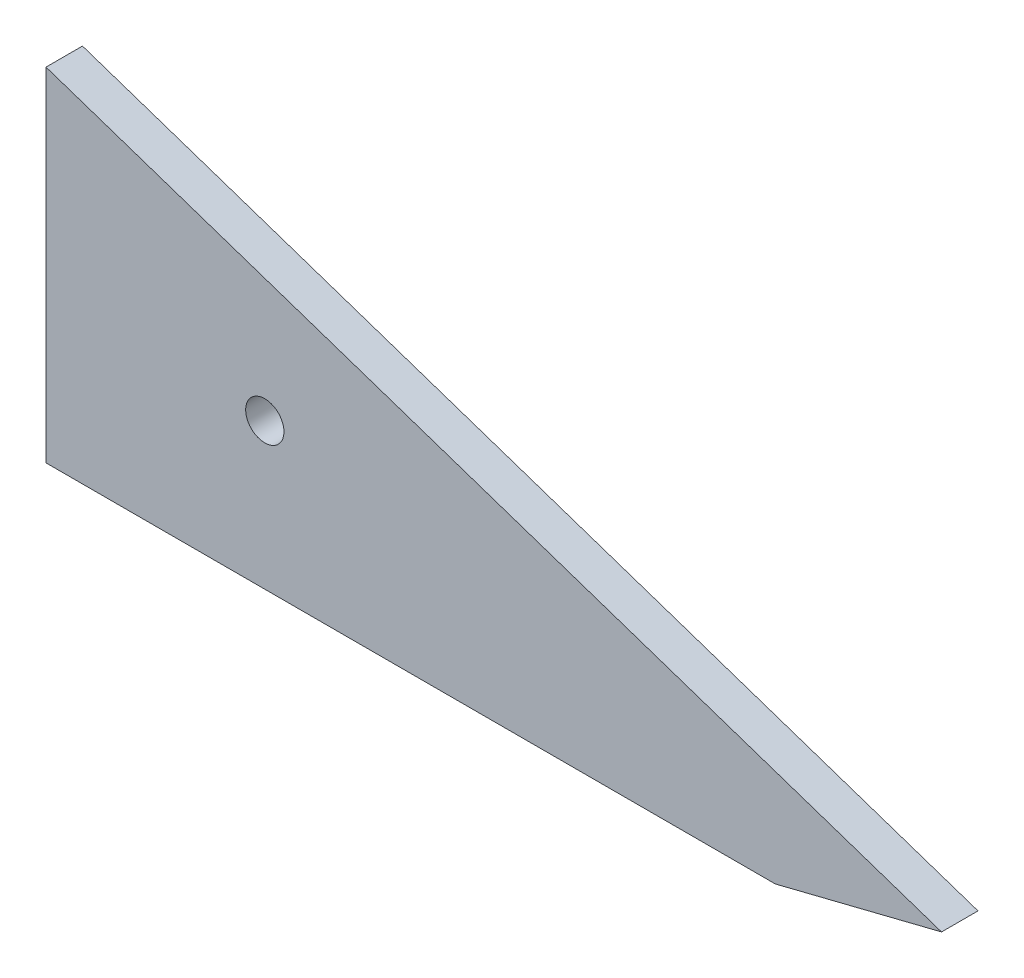
SolidWorks part; units mm, degrees
material "A516 Gr. 70 (Killed Carbon Steel)"
ref_plane "Front Plane" through (0, 0, 0) normal (0, 0, 1) x (1, 0, 0)
ref_plane "Top Plane" through (0, 0, 0) normal (0, 1, 0) x (1, 0, 0)
ref_plane "Right Plane" through (0, 0, 0) normal (1, 0, 0) x (0, 0, -1)
sketch "Sketch1" plane through (0, 0, 0) normal (0, 0, 1) x (1, 0, 0)
  line L0 (0, 0) -> (200, 0)
  line L1 (220, 5) -> (220, 20) construction
  line L2 (220, 20) -> (0, 94)
  line L3 (0, 94) -> (0, 0)
  line L4 (0, 0) -> (200, 0) construction
  line L5 (200, 0) -> (220, 5)
  line L6 (220, 0) -> (220, 5) construction
  line L7 (200, 0) -> (220, 0) construction
  line L8 (220, 5) -> (245.5814, 11.3953)
  line L9 (245.5814, 11.3953) -> (220, 20)
  dimension "D1" = 5
  dimension "D2" = 200
  dimension "D3" = 94
  dimension "D4" = 20
  dimension "D5" = 20
extrude "Boss-Extrude1" add sketch "Sketch1" along normal blind 10
hole_wizard "M12x1.5 Tapped Hole2" positions "3DSketch2" profile "Sketch6" tap size "M12x1.5" standard "ANSI Metric"
sketch3d "3DSketch2"
  line L0 (0, 0, 10) -> (200, 0, 10) construction
  line L1 (0, 94, 10) -> (0, 0, 10) construction
  point P0 (60, 40, 10)
  dimension "D1" = 60
  dimension "D2" = 40
sketch "Sketch6" plane through (60, 40, 10) normal (1, 0, 0) x (0, -1, 0)
  line L0 (0, 0) -> (0, 31.6545)
  line L1 (0, 31.6545) -> (5.25, 28.5)
  line L2 (5.25, 28.5) -> (5.25, 0)
  line L5 (5.25, 0) -> (0, 0)
  line L10 (0, 31.6545) -> (-5.25, 28.5) construction
  line L11 (0, -6.35) -> (0, 107.95) construction
  dimension "Tap Drill Dia." = 10.5
  dimension "Tap Drill Depth" = 28.5
  dimension "Drill Angle" = 118
cosmetic thread "Hole Thread2" parameters "D1"=24, "D2"=12
